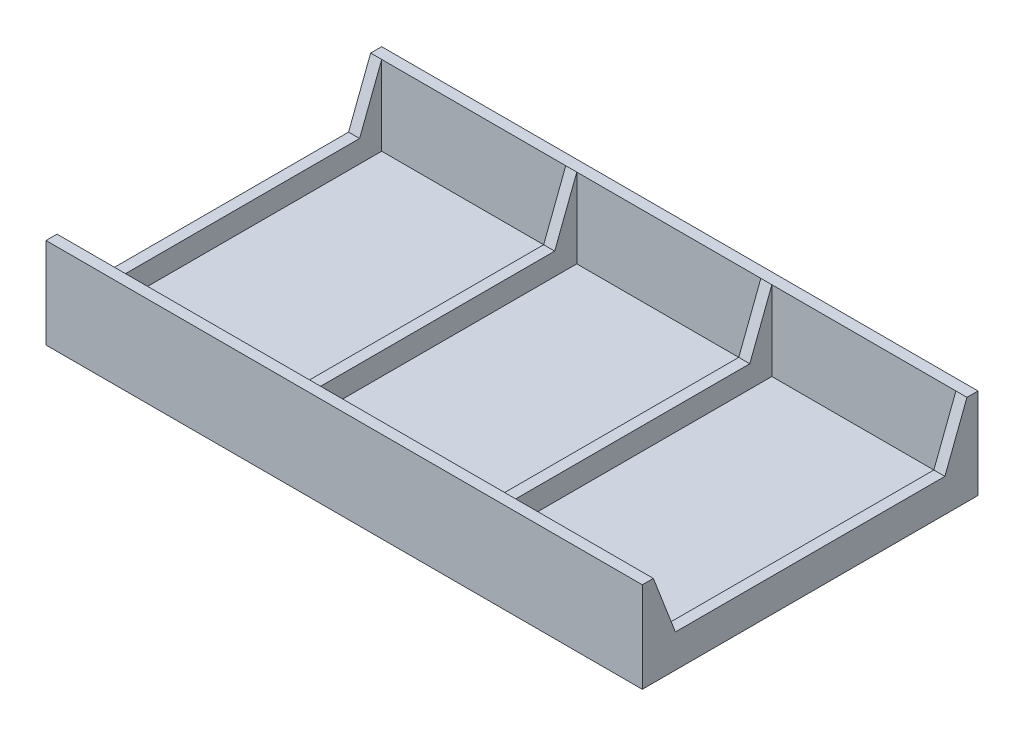
SolidWorks part; units mm, degrees
ref_plane "Front Plane" through (0, 0, 0) normal (0, 0, 1) x (1, 0, 0)
ref_plane "Top Plane" through (0, 0, 0) normal (0, 1, 0) x (1, 0, 0)
ref_plane "Right Plane" through (0, 0, 0) normal (1, 0, 0) x (0, 0, -1)
sketch "Sketch1" plane through (0, 0, 0) normal (0, 1, 0) x (1, 0, 0)
  line L1 (0, 0) -> (68.58, 0)
  line L2 (0, 0) -> (0, 38.608)
  line L3 (0, 38.608) -> (68.58, 38.608)
  line L4 (68.58, 0) -> (68.58, 38.608)
  dimension "D1" = 38.608
  dimension "D2" = 68.58
extrude "Boss-Extrude1" add sketch "Sketch1" along normal blind 1.27
sketch "Sketch2" plane through (0, 1.27, 0) normal (0, 1, 0) x (1, 0, 0)
  line L0 (68.58, 0) -> (68.58, 38.608) construction
  line L1 (0, 38.608) -> (68.58, 38.608)
  line L2 (0, 38.608) -> (0, 37.338)
  line L3 (0, 37.338) -> (68.58, 37.338)
  line L4 (68.58, 38.608) -> (68.58, 37.338)
  line L6 (0, 0) -> (68.58, 0)
  line L7 (0, 0) -> (0, 1.27)
  line L8 (0, 1.27) -> (68.58, 1.27)
  line L9 (68.58, 0) -> (68.58, 1.27)
  dimension "D1" = 1.27
  dimension "D2" = 1.27
extrude "Boss-Extrude2" add sketch "Sketch2" along normal blind 9.144
sketch "Sketch4" plane through (0, 1.27, 0) normal (0, 1, 0) x (1, 0, 0)
  line L0 (68.58, 1.27) -> (0, 1.27) construction
  line L1 (0, 37.338) -> (1.27, 37.338)
  line L2 (0, 37.338) -> (0, 1.27)
  line L3 (0, 1.27) -> (1.27, 1.27)
  line L4 (1.27, 37.338) -> (1.27, 1.27)
  line L5 (68.58, 1.27) -> (0, 1.27) construction
  line L6 (22.4367, 1.27) -> (23.7067, 1.27)
  line L7 (22.4367, 1.27) -> (22.4367, 37.338)
  line L8 (22.4367, 37.338) -> (23.7067, 37.338)
  line L9 (23.7067, 1.27) -> (23.7067, 37.338)
  line L10 (0, 37.338) -> (68.58, 37.338) construction
  line L11 (68.58, 1.27) -> (0, 1.27) construction
  line L12 (44.8733, 37.338) -> (46.1433, 37.338)
  line L13 (44.8733, 37.338) -> (44.8733, 1.27)
  line L14 (44.8733, 1.27) -> (46.1433, 1.27)
  line L15 (46.1433, 37.338) -> (46.1433, 1.27)
  line L16 (0, 37.338) -> (68.58, 37.338) construction
  line L17 (68.58, 1.27) -> (67.31, 1.27)
  line L18 (68.58, 1.27) -> (68.58, 37.338)
  line L19 (68.58, 37.338) -> (67.31, 37.338)
  line L20 (67.31, 1.27) -> (67.31, 37.338)
  line L21 (1.27, 19.304) -> (22.4367, 19.304) construction
  line L22 (23.7067, 19.304) -> (44.8733, 19.304) construction
  line L23 (46.1433, 19.304) -> (67.31, 19.304) construction
  dimension "D1" = 1.27
extrude "Boss-Extrude4" add sketch "Sketch4" along normal blind 2.54
chamfer "Chamfer2" distance 6.604 angle 21.038 8 edges at (67.945, 3.81, -37.338) (67.945, 3.81, -1.27) (45.5083, 3.81, -1.27) (45.5083, 3.81, -37.338) (23.0717, 3.81, -37.338) (23.0717, 3.81, -1.27) (0.635, 3.81, -1.27) (0.635, 3.81, -37.338) first distance on face at (34.29, 3.683, -37.338) first distance on face at (34.29, 3.683, -1.27)
